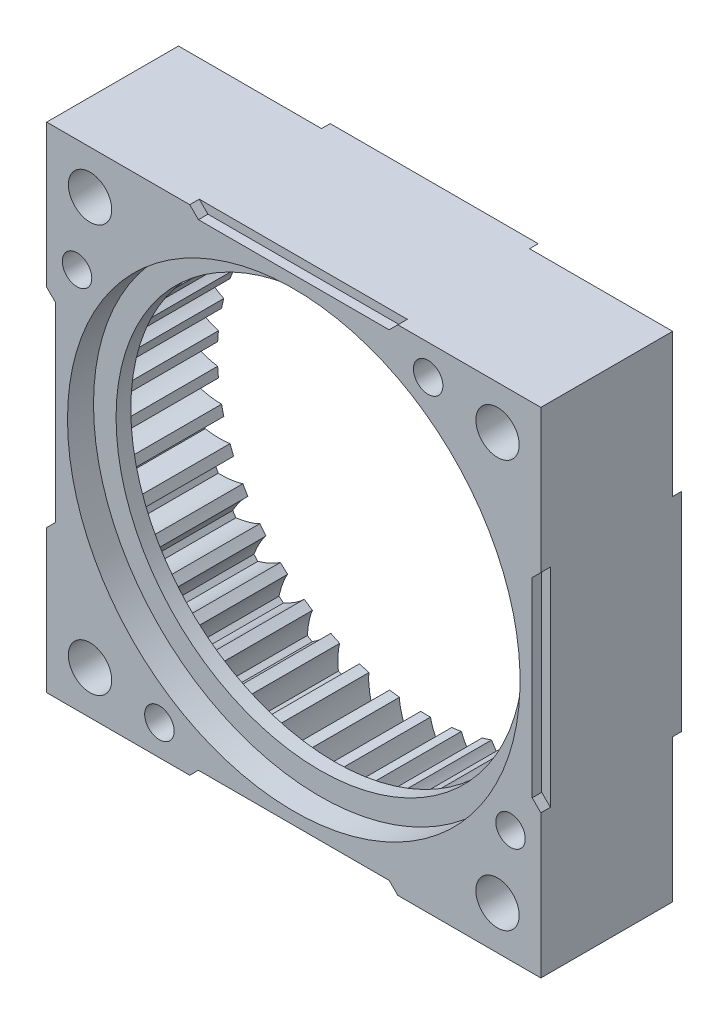
SolidWorks part; units mm, degrees
note: The reader was unsure of these and kept them because the rebuilt part matched: shared geometry of "Sketch5<5>", "Sketch6<3>".
ref_plane "Front Plane" through (0, 0, 0) normal (0, 0, 1) x (1, 0, 0)
ref_plane "Top Plane" through (0, 0, 0) normal (0, 1, 0) x (1, 0, 0)
ref_plane "Right Plane" through (0, 0, 0) normal (1, 0, 0) x (0, 0, -1)
ref_axis "Axis1" through (0, 0, -88.99) along (0, 0, 1)
sketch "Sketch1" plane through (0, 0, 0) normal (0, 0, 1) x (1, 0, 0)
  circle A0 centre (0, 0) radius 26.7
  circle A1 centre (0, 0) radius 29.4
extrude "LaShenA" add sketch "Sketch1" along normal blind 10.5
sketch "SketchA" plane through (0, 0, 10.5) normal (0, 0, 1) x (1, 0, 0)
  arc A0 (0.568, 24) -> (-0.568, 24) centre (0, 0) ccw
  arc A1 (1.9411, 27.0887) -> (-1.9411, 27.0887) centre (0, 0) ccw
  circle A2 centre (0, 0) radius 23.6803 construction
  circle A3 centre (0, 0) radius 24 construction
  circle A4 centre (0, 0) radius 26.7 construction
  circle A5 centre (0, 0) radius 25.2 construction
  spline S0 degree 3 poles (0.568, 24) (0.5838, 24.0765) (0.6056, 24.1796) (0.6378, 24.3103) (0.6601, 24.3951) (0.6854, 24.4853) (0.7137, 24.5808) (0.7454, 24.6814) (0.7805, 24.7871) (0.8192, 24.8979) (0.8616, 25.0135) (0.9081, 25.134) (0.9586, 25.2592) (1.0134, 25.3891) (1.0727, 25.5235) (1.1365, 25.6623) (1.205, 25.8054) (1.2785, 25.9527) (1.357, 26.1041) (1.4407, 26.2594) (1.5297, 26.4185) (1.6241, 26.5814) (1.7596, 26.8066) (1.8668, 26.9755) (1.9411, 27.0887) knots 0 0 0 0 0.068895 0.092963 0.118769 0.146313 0.175597 0.206619 0.239379 0.273878 0.310116 0.348092 0.387807 0.429261 0.472453 0.517384 0.564054 0.612462 0.662609 0.714494 0.768118 0.82348 0.880582 1 1 1 1
  spline S1 degree 3 poles (-0.568, 24) (-0.5838, 24.0765) (-0.6056, 24.1796) (-0.6378, 24.3103) (-0.6601, 24.3951) (-0.6854, 24.4853) (-0.7137, 24.5808) (-0.7454, 24.6814) (-0.7805, 24.7871) (-0.8192, 24.8979) (-0.8616, 25.0135) (-0.9081, 25.134) (-0.9586, 25.2592) (-1.0134, 25.3891) (-1.0727, 25.5235) (-1.1365, 25.6623) (-1.205, 25.8054) (-1.2785, 25.9527) (-1.357, 26.1041) (-1.4407, 26.2594) (-1.5297, 26.4185) (-1.6241, 26.5814) (-1.7596, 26.8066) (-1.8668, 26.9755) (-1.9411, 27.0887) knots 0 0 0 0 0.068895 0.092963 0.118769 0.146313 0.175597 0.206619 0.239379 0.273878 0.310116 0.348092 0.387807 0.429261 0.472453 0.517384 0.564054 0.612462 0.662609 0.714494 0.768118 0.82348 0.880582 1 1 1 1
  dimension "Db" = 47.3605
  dimension "Da" = 48
  dimension "Df" = 53.4
  dimension "Dn" = 50.4
extrude "Cut-ExtrudeA" add sketch "SketchA" against normal blind 10.5
pattern_circular "www.KYTool.cn" count 42 over 360 about axis through (0, 0, -88.99) along (0, 0, 1) of "Cut-ExtrudeA"
sketch "Sketch4" plane through (0, 0, 0) normal (0, 1, 0) x (1, 0, 0)
  line L0 (-29.4, -10.5) -> (-29.4, -15.2)
  line L1 (-29.4, -15.2) -> (-26.1, -15.2)
  line L2 (-26.1, -15.2) -> (-26.1, -12.2)
  line L3 (-26.1, -12.2) -> (-23.5, -12.2)
  line L4 (-23.5, -12.2) -> (-23.5, -10.5)
  line L5 (-23.5, -10.5) -> (-29.4, -10.5)
  line L6 (0, 88.99) -> (0, -88.99) construction
  line L7 (29.4, 0) -> (-29.4, 0) construction
  line L8 (29.4, -10.5) -> (29.4, 0) construction
  dimension "D1" = 15.2
  dimension "D2" = 58.8
  dimension "D3" = 3
  dimension "D4" = 26.1
  dimension "D5" = 23.5
revolve "Revolve1" add sketch "Sketch4" angle 360 about axis through (0, 0, -88.99) along (0, 0, 1)
sketch "Sketch5" plane through (0, 0, 0) normal (0, 0, -1) x (-1, 0, 0)
  line L1 (28.5, -28.5) -> (-28.5, -28.5)
  line L2 (28.5, -28.5) -> (28.5, 28.5)
  line L3 (28.5, 28.5) -> (-28.5, 28.5)
  line L4 (-28.5, -28.5) -> (-28.5, 28.5)
  line L5 (28.5, -28.5) -> (-28.5, 28.5) construction
  line L6 (28.5, 28.5) -> (-28.5, -28.5) construction
  circle A1 centre (0, 0) radius 29.4
  circle A2 centre (0, 0) radius 29.4
  dimension "D2" = 57
  dimension "D1" = 0
extrude "Cut-Extrude2" cut sketch "Sketch5" against normal through all contours L2 A2 | L1 A2 | L4 A2 | L3 A2
extrude "Boss-Extrude3" add sketch "Sketch5<5>" against normal up to surface (15.2 mm away) contours A2 L2 L3 | A2 L3 L4 | A2 L4 L1 | A2 L1 L2 up to face at (-26.1, 0, 15.2)
sketch "Sketch5<5>" plane through (0, 0, 0) normal (0, 0, -1) x (-1, 0, 0) same geometry as "Sketch5"
sketch "Sketch6" plane through (0, 0, 0) normal (0, 0, -1) x (-1, 0, 0)
  line L0 (0, 0) -> (0, 42.6707) construction
  line L1 (11, 27.5) -> (-11, 27.5)
  line L2 (-11, 27.5) -> (-12, 28.5)
  line L3 (28.5, 28.5) -> (-28.5, 28.5) construction
  line L4 (28.5, -28.5) -> (28.5, 28.5)
  line L5 (28.5, 28.5) -> (-28.5, 28.5)
  line L6 (-28.5, 28.5) -> (-28.5, -28.5)
  line L7 (-28.5, -28.5) -> (28.5, -28.5)
  line L8 (28.5, -28.5) -> (28.5, 28.5)
  line L9 (28.5, 28.5) -> (-23.5, 28.5)
  line L10 (-28.5, 23.5) -> (-28.5, -28.5)
  line L11 (-28.5, -28.5) -> (28.5, -28.5)
  line L12 (11, 27.5) -> (12, 28.5)
  circle A0 centre (-23.5, 23.5) radius 2.5
  circle A1 centre (-15.5, 25) radius 1.7
  arc A2 (-28.5, 23.5) -> (-23.5, 28.5) centre (-23.5, 23.5) cw
  point P15 (-12.4443, 28.5)
  point P21 (0, 27.5)
  dimension "D2" = 5
  dimension "D3" = 5
  dimension "D6" = 3.4
  dimension "D4" = 8
  dimension "D5" = 3.5
  dimension "D7" = 11
  dimension "D8" = 135
  dimension "D9" = 1
  dimension "D1" = 0
extrude "Cut-Extrude3" cut sketch "Sketch6" against normal through all contours A0 | A1
extrude "Boss-Extrude4" add sketch "Sketch6<3>" along normal blind 1 contours L1 L0 L9 L2 | L0 L1 L12 L9
sketch "Sketch6<3>" plane through (0, 0, 0) normal (0, 0, -1) x (-1, 0, 0) same geometry as "Sketch6"
fillet "Fillet1" radius 0.2 1 edges at (0, 27.5, -1)
sketch "Sketch7" plane through (0, 0, 15.2) normal (0, 0, 1) x (1, 0, 0)
  line L0 (11, 27.5) -> (12, 28.5) construction
  line L1 (-11, 27.5) -> (11, 27.5) construction
  line L2 (-11, 27.5) -> (-12, 28.5) construction
  line L3 (11, 27.5) -> (12, 28.5)
  line L4 (-28.5, 28.5) -> (-28.5, -28.5)
  line L5 (23.5, 28.5) -> (-28.5, 28.5)
  line L6 (28.5, -28.5) -> (28.5, 23.5)
  line L7 (-28.5, -28.5) -> (28.5, -28.5)
  line L8 (-28.5, 28.5) -> (-28.5, -28.5)
  line L9 (23.5, 28.5) -> (-28.5, 28.5)
  line L10 (28.5, -28.5) -> (28.5, 23.5)
  line L11 (-28.5, -28.5) -> (28.5, -28.5)
  line L12 (-11, 27.5) -> (11, 27.5)
  line L13 (-11, 27.5) -> (-12, 28.5)
  circle A1 centre (15.5, 25) radius 1.7
  circle A2 centre (15.5, 25) radius 1.7
  circle A3 centre (23.5, 23.5) radius 2.5
  circle A4 centre (23.5, 23.5) radius 2.5
  arc A5 (28.5, 23.5) -> (23.5, 28.5) centre (23.5, 23.5) ccw
  arc A6 (28.5, 23.5) -> (23.5, 28.5) centre (23.5, 23.5) ccw
  line M11 (28.5, 28.5) -> (-28.5, 28.5)
  dimension "D1" = 0
  dimension "D2" = 0
  dimension "D3" = 0
extrude "Cut-Extrude4" cut sketch "Sketch7" against normal blind 1.1 contours L13 L12 L3 M11
pattern_circular "CirPattern2" count 4 over 360 about axis through (0, 0, 0) along (0, 0, 1) of "Cut-Extrude4", "Boss-Extrude4", "Fillet1", "Cut-Extrude3"
